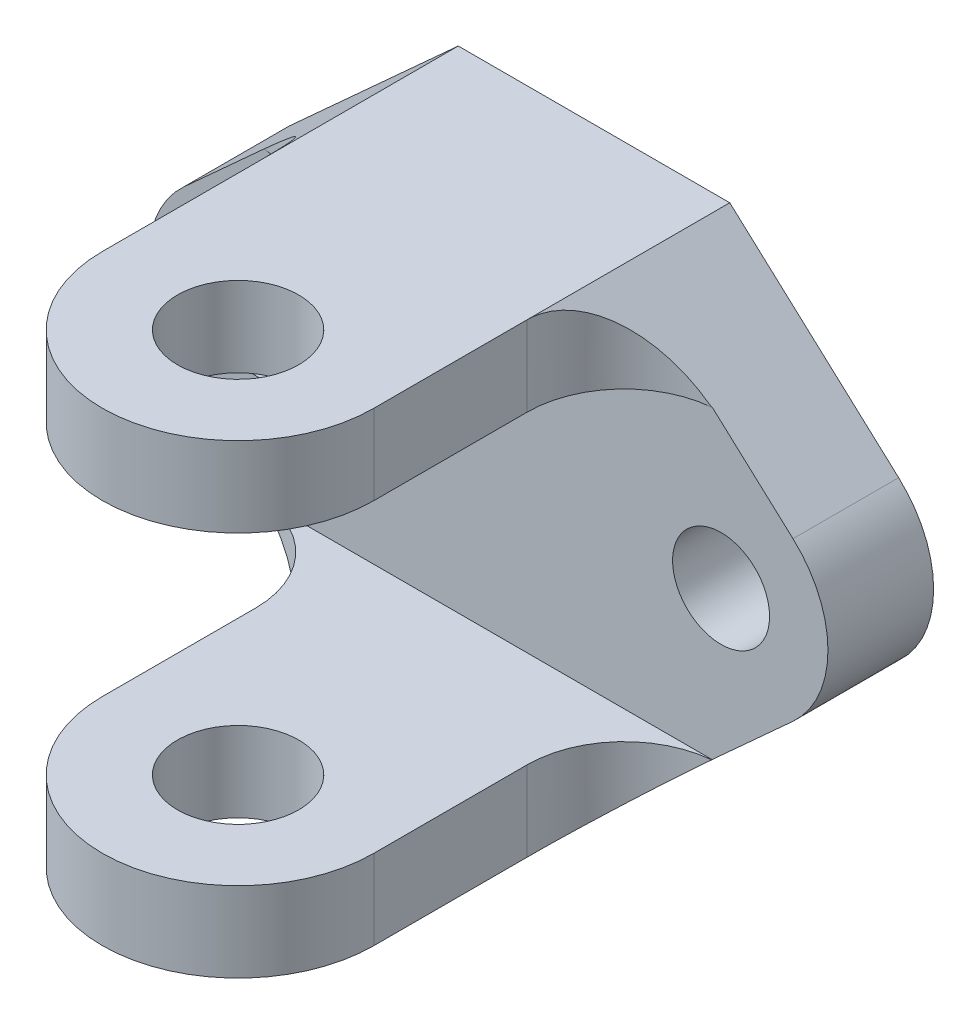
SolidWorks part; units mm, degrees
material "7075-T6 (SN)"
ref_plane "Front Plane" through (0, 0, 0) normal (0, 0, 1) x (1, 0, 0)
ref_plane "Top Plane" through (0, 0, 0) normal (0, 1, 0) x (1, 0, 0)
ref_plane "Right Plane" through (0, 0, 0) normal (1, 0, 0) x (0, 0, -1)
sketch "Sketch1" plane through (0, 0, 0) normal (0, 0, 1) x (1, 0, 0)
  line L0 (15.24, 0) -> (-15.24, 0) construction
  line L1 (-23.24, -15.24) -> (23.24, -15.24)
  line L2 (-23.24, -15.24) -> (-23.24, 15.24)
  line L3 (-23.24, 15.24) -> (23.24, 15.24)
  line L4 (23.24, -15.24) -> (23.24, 15.24)
  line L5 (-23.24, -15.24) -> (23.24, 15.24) construction
  line L6 (-23.24, 15.24) -> (23.24, -15.24) construction
  circle A0 centre (15.24, 0) radius 3.175
  circle A1 centre (-15.24, 0) radius 3.175
  point P0 (0, 0)
  dimension "D1" = 6.35
  dimension "D2" = 30.48
  dimension "D3" = 8
  dimension "D4" = 15.24
extrude "Boss-Extrude1" add sketch "Sketch1" along normal blind 9.46
sketch "Sketch2" plane through (0, 0, 9.46) normal (0, 0, 1) x (1, 0, 0)
  line L0 (-15.24, 0) -> (15.24, 0) construction
  line L2 (-23.24, 10) -> (23.24, 10)
  line L3 (-23.24, 10) -> (-23.24, 15.24)
  line L4 (-23.24, 15.24) -> (23.24, 15.24)
  line L5 (23.24, 10) -> (23.24, 15.24)
  line L6 (-23.24, 10) -> (23.24, 15.24) construction
  line L7 (-23.24, 15.24) -> (23.24, 10) construction
  line L8 (-23.24, 15.24) -> (-23.24, -15.24) construction
  line L9 (23.24, -10) -> (23.24, -15.24)
  line L10 (-23.24, -10) -> (-23.24, -15.24)
  line L11 (-23.24, -15.24) -> (23.24, -10) construction
  line L12 (-23.24, -10) -> (23.24, -15.24) construction
  line L13 (-23.24, -10) -> (23.24, -10)
  line L14 (-23.24, -15.24) -> (23.24, -15.24)
  circle A0 centre (-15.24, 0) radius 3.175 construction
  circle A1 centre (15.24, 0) radius 3.175 construction
  point P6 (0, 12.62)
  point P21 (0, -12.62)
  dimension "D1" = 20
extrude "Boss-Extrude2" add sketch "Sketch2" along normal blind 53
sketch "Sketch3" plane through (0, 0, 0) normal (0, 1, 0) x (1, 0, 0)
  point P0 (0, -25.8481)
  dimension "D1" = 25.8481
ref_point "UBJ Point"
sketch "Sketch4" plane through (0, 0, 0) normal (0, 1, 0) x (1, 0, 0)
  circle A0 centre (0, -25.8481) radius 3.9688
  dimension "D1" = 7.9375
extrude "Cut-Extrude1" cut sketch "Sketch4" against normal up to surface and the other way up to surface up to face at (0, -15.24, 31.23) other way up to face at (0, 15.24, 31.23)
sketch "Sketch5" plane through (0, 0, 0) normal (0, 1, 0) x (1, 0, 0)
  line L0 (23.24, -9.46) -> (8.2363, -31.4641)
  line L1 (-8.2363, -31.4641) -> (-23.24, -9.46)
  line L4 (23.24, 0) -> (-23.24, 0)
  line L5 (-23.24, 0) -> (-23.24, -62.46)
  line L6 (-23.24, -62.46) -> (23.24, -62.46)
  line L7 (23.24, -62.46) -> (23.24, 0)
  line L9 (-23.24, -9.46) -> (-23.24, -62.46)
  line L10 (-23.24, -62.46) -> (23.24, -62.46)
  line L11 (23.24, -62.46) -> (23.24, -9.46)
  line L12 (23.24, -9.46) -> (-23.24, -9.46)
  line L13 (23.24, -62.46) -> (23.24, -9.46)
  line L14 (-23.24, -62.46) -> (23.24, -62.46)
  line L15 (-23.24, -9.46) -> (-23.24, -62.46)
  line L17 (23.24, -62.46) -> (23.24, -9.46)
  line L18 (-23.24, -62.46) -> (23.24, -62.46)
  line L19 (-23.24, -9.46) -> (-23.24, -62.46)
  arc A0 (-8.2363, -31.4641) -> (8.2363, -31.4641) centre (0, -25.8481) ccw
  circle A1 centre (0, -25.8481) radius 3.9688 construction
  circle A2 centre (0, -25.8481) radius 3.9688 construction
  dimension "D3" = 6
  dimension "D1" = 0
  dimension "D2" = 0
extrude "Cut-Extrude2" [suppressed] cut sketch "Sketch5" against normal up to surface and the other way up to surface contours A0 L1 L9 L10 L11 L0
sketch "Sketch6" plane through (0, 0, 0) normal (0, 1, 0) x (1, 0, 0)
  line L0 (-8.89, -25.8481) -> (-8.89, -17.46)
  line L1 (8.89, -25.8481) -> (8.89, -17.46)
  line L2 (-16.89, -9.46) -> (-23.24, -9.46)
  line L3 (-8.89, -17.46) -> (-8.89, -9.46)
  line L4 (23.24, -9.46) -> (-23.24, -9.46)
  line L5 (-23.24, -9.46) -> (-23.24, -62.46)
  line L6 (-23.24, -62.46) -> (23.24, -62.46)
  line L7 (23.24, -62.46) -> (23.24, -9.46)
  line L8 (23.24, -9.46) -> (16.89, -9.46)
  line L9 (-23.24, -9.46) -> (-23.24, -62.46)
  line L10 (-23.24, -62.46) -> (23.24, -62.46)
  line L11 (23.24, -62.46) -> (23.24, -9.46)
  line L12 (-8.89, -9.46) -> (-16.89, -9.46)
  line L13 (8.89, -17.46) -> (8.89, -9.46)
  line L14 (8.89, -9.46) -> (16.89, -9.46)
  arc A0 (-8.89, -25.8481) -> (8.89, -25.8481) centre (0, -25.8481) ccw
  circle A1 centre (0, -25.8481) radius 3.9688 construction
  arc A2 (-8.89, -17.46) -> (-16.89, -9.46) centre (-16.89, -17.46) ccw construction
  arc A3 (8.89, -17.46) -> (16.89, -9.46) centre (16.89, -17.46) cw construction
  dimension "D2" = 8.89
  dimension "D3" = 8
  dimension "D1" = 0
extrude "Cut-Extrude3" cut sketch "Sketch6" against normal up to surface and the other way up to surface contours A0 L3 L12 L2 L9 L10 L11 L8 L14 L13 region at (0, 0, 38.9489) up to face at (0, -15.24, 29.8169) other way up to face at (0, 15.24, 21.8794)
fillet "Fillet1" [suppressed] radius 12.7
sketch "Sketch7" plane through (0, 0, 0) normal (0, 0, 1) x (1, 0, 0)
  line L0 (-15.24, 7) -> (-8.89, 7)
  line L1 (-15.24, -7) -> (-8.89, -7)
  line L2 (-8.89, 10) -> (-8.89, 7)
  line L3 (-8.89, -10) -> (-8.89, -7)
  line L4 (0, 10.3988) -> (0, -8.4154) construction
  line L5 (8.89, -10) -> (8.89, -7)
  line L6 (8.89, 10) -> (8.89, 15.24)
  line L7 (23.24, 15.24) -> (23.24, -15.24)
  line L8 (8.89, -10) -> (8.89, -15.24)
  line L9 (8.89, 10) -> (8.89, 7)
  line L10 (15.24, 7) -> (8.89, 7)
  line L11 (15.24, -7) -> (8.89, -7)
  line L12 (8.89, 10) -> (-8.89, 10)
  line L15 (-23.24, 15.24) -> (-23.24, -15.24)
  line L18 (-8.89, -10) -> (8.89, -10)
  line L21 (23.24, -15.24) -> (23.24, 15.24)
  line L27 (-23.24, 15.24) -> (-23.24, -15.24)
  line L33 (23.24, -15.24) -> (23.24, 15.24)
  line L36 (-8.89, 15.24) -> (-8.89, 10)
  line L37 (-8.89, -10) -> (-8.89, -15.24)
  line L48 (-8.89, 10) -> (-8.89, 15.24)
  line L49 (-8.89, -15.24) -> (-8.89, -10)
  line L52 (-8.89, 15.24) -> (-23.24, 15.24)
  line L53 (-8.89, 15.24) -> (-23.24, 15.24)
  line L54 (-23.24, -15.24) -> (-8.89, -15.24)
  line L55 (-23.24, -15.24) -> (-8.89, -15.24)
  line L56 (8.89, -10) -> (8.89, -15.24)
  line L57 (8.89, -15.24) -> (23.24, -15.24)
  line L58 (8.89, -15.24) -> (23.24, -15.24)
  line L59 (23.24, 15.24) -> (8.89, 15.24)
  line L60 (23.24, 15.24) -> (8.89, 15.24)
  line L61 (8.89, 15.24) -> (8.89, 10)
  arc A0 (-15.24, 7) -> (-15.24, -7) centre (-15.24, 0) ccw
  circle A1 centre (-15.24, 0) radius 3.175 construction
  arc A2 (15.24, 7) -> (15.24, -7) centre (15.24, 0) cw
  dimension "D2" = 7
  dimension "D1" = 0
extrude "Cut-Extrude4" cut sketch "Sketch7" along normal up to surface (9.46 mm away) contours A0 L0 L2 L53 L27 L55 L3 L1 | L10 A2 L11 L5 L7 L9 region at (-22.5769, 0, 0) region at (9.2269, 12.62, 0) up to face at (18.415, 0, 9.46)
fillet "Fillet2" [suppressed] radius 5
sketch "Sketch8" plane through (0, 0, 0) normal (0, 0, 1) x (1, 0, 0)
  line L0 (15.24, 7) -> (8.89, 7) construction
  line L1 (8.89, 15.24) -> (8.89, 7) construction
  line L2 (15.24, 7) -> (8.89, 7)
  line L3 (8.89, 15.24) -> (8.89, 7)
  line L4 (6.7586, 0) -> (-5.803, 0) construction
  line L5 (0, 7.1591) -> (0, -7.1591) construction
  line L6 (8.89, 15.24) -> (19.9505, 5.1779)
  line L7 (-8.89, 15.24) -> (-8.89, 7)
  line L8 (-15.24, 7) -> (-8.89, 7)
  line L9 (-8.89, 15.24) -> (-19.9505, 5.1779)
  line L10 (-8.89, -15.24) -> (-19.9505, -5.1779)
  line L11 (-15.24, -7) -> (-8.89, -7)
  line L12 (-8.89, -15.24) -> (-8.89, -7)
  line L13 (8.89, -15.24) -> (8.89, -7)
  line L14 (15.24, -7) -> (8.89, -7)
  line L15 (8.89, -15.24) -> (19.9505, -5.1779)
  arc A0 (15.24, -7) -> (15.24, 7) centre (15.24, 0) ccw construction
  arc A1 (19.9505, 5.1779) -> (15.24, 7) centre (15.24, 0) ccw
  arc A2 (-19.9505, 5.1779) -> (-15.24, 7) centre (-15.24, 0) cw
  arc A3 (-19.9505, -5.1779) -> (-15.24, -7) centre (-15.24, 0) ccw
  arc A4 (19.9505, -5.1779) -> (15.24, -7) centre (15.24, 0) cw
extrude "Boss-Extrude3" add sketch "Sketch8" along normal up to surface (9.46 mm away) contours L15 A4 L14 L13 | A3 L10 L12 L11 | L6 A1 L2 L3 | L9 A2 L8 L7 region at (-12.0433, -9.6757, 0) region at (12.0433, -9.6757, 0) up to face at (0, 0, 9.46)
fillet "Fillet3" radius 6.35 4 edges at (8.89, 12.62, 9.46) (-8.89, 12.62, 9.46) (8.89, -12.62, 9.46) (-8.89, -12.62, 9.46)
sketch "Sketch10" plane through (0, 0, 0) normal (0, 0, 1) x (1, 0, 0)
  line L5 (-8.89, 15.24) -> (-19.9505, 5.1779)
  line L6 (-8.89, 15.24) -> (-19.9505, 5.1779)
  line L7 (8.89, 15.24) -> (-8.89, 15.24)
  line L8 (19.9505, 5.1779) -> (8.89, 15.24)
  line L9 (8.89, -15.24) -> (19.9505, -5.1779)
  line L10 (-8.89, -15.24) -> (8.89, -15.24)
  line L13 (8.89, 15.24) -> (-8.89, 15.24)
  line L14 (19.9505, 5.1779) -> (8.89, 15.24)
  line L15 (8.89, -15.24) -> (19.9505, -5.1779)
  line L16 (-8.89, -15.24) -> (8.89, -15.24)
  line L18 (-19.9505, -5.1779) -> (-8.89, -15.24)
  line L19 (-19.9505, -5.1779) -> (-8.89, -15.24)
  arc A2 (-19.9505, 5.1779) -> (-19.9505, -5.1779) centre (-15.24, 0) ccw
  arc A3 (19.9505, -5.1779) -> (19.9505, 5.1779) centre (15.24, 0) ccw
  arc A5 (19.9505, -5.1779) -> (19.9505, 5.1779) centre (15.24, 0) ccw
  arc A6 (-19.9505, 5.1779) -> (-19.9505, -5.1779) centre (-15.24, 0) ccw
  dimension "D1" = 0
extrude "Cut-Extrude5" cut sketch "Sketch10" along normal blind 2.54
